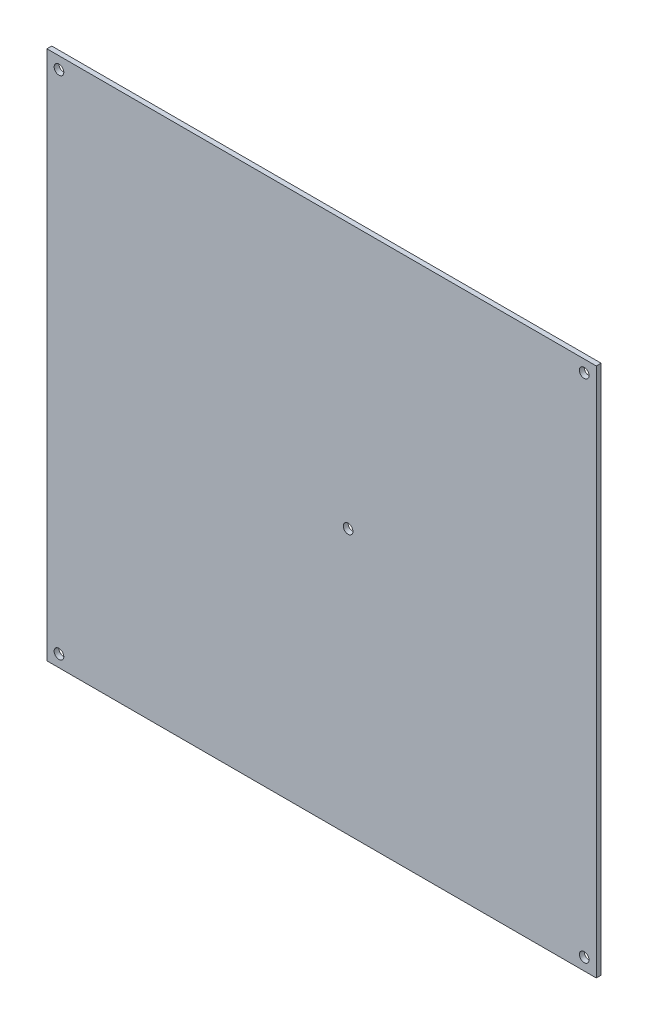
SolidWorks part; units mm, degrees
ref_plane "Alzado" through (0, 0, 0) normal (0, 0, 1) x (1, 0, 0)
ref_plane "Planta" through (0, 0, 0) normal (0, 1, 0) x (1, 0, 0)
ref_plane "Vista lateral" through (0, 0, 0) normal (1, 0, 0) x (0, 0, -1)
sketch "Sketch1" plane through (0, 0, 0) normal (0, 0, 1) x (1, 0, 0)
  line L1 (-83.7545, 63.3993) -> (30.2455, 63.3993)
  line L2 (-83.7545, 63.3993) -> (-83.7545, -46.6007)
  line L3 (-83.7545, -46.6007) -> (30.2455, -46.6007)
  line L4 (30.2455, 63.3993) -> (30.2455, -46.6007)
  line L5 (-83.7545, 63.3993) -> (30.2455, -46.6007) construction
  line L6 (-83.7545, -46.6007) -> (30.2455, 63.3993) construction
  point P0 (-26.7545, 8.3993)
  dimension "D1" = 114
  dimension "D2" = 110
extrude "Boss-Extrude1" add sketch "Sketch1" along normal blind 1
sketch "Sketch2" plane through (0, 0, 1) normal (0, 0, 1) x (1, 0, 0)
  line L0 (-83.7545, 63.3993) -> (-83.7545, -46.6007) construction
  line L9 (30.2455, 63.3993) -> (-83.7545, 63.3993) construction
  line L10 (30.2455, -46.6007) -> (30.2455, 63.3993) construction
  line L11 (-83.7545, -46.6007) -> (30.2455, -46.6007) construction
  circle A1 centre (-81.2545, 60.8993) radius 1
  circle A2 centre (27.7455, 60.8993) radius 1
  circle A3 centre (27.7455, -44.1007) radius 1
  circle A4 centre (-81.2545, -44.1007) radius 1
  dimension "D1" = 2.5
  dimension "D3" = 2.5
  dimension "D5" = 2.5
  dimension "D2" = 2.5
  dimension "D4" = 2.5
  dimension "D6" = 2.5
extrude "Cut-Extrude1" cut sketch "Sketch2" against normal through all
sketch "Sketch3" plane through (0, 0, 0) normal (0, 0, -1) x (-1, 0, 0)
  line L0 (81.2545, 60.8993) -> (81.2545, 11.8993) construction
  line L1 (81.2545, 11.8993) -> (28.7545, 11.8993) construction
  circle A0 centre (28.7545, 11.8993) radius 1
  dimension "D1" = 49
  dimension "D2" = 52.5
extrude "Cut-Extrude2" cut sketch "Sketch3" against normal blind 10
sketch "Sketch4" plane through (0, 0, 1) normal (0, 0, 1) x (1, 0, 0)
  line L1 (-35.1672, 16.8899) -> (-19.4323, 16.8899)
  line L2 (-35.1672, 16.8899) -> (-35.1672, -3.8303)
  line L3 (-35.1672, -3.8303) -> (-19.4323, -3.8303)
  line L4 (-19.4323, 16.8899) -> (-19.4323, -3.8303)
extrude "Boss-Extrude2" add sketch "Sketch4" against normal through all
sketch "Sketch6" plane through (0, 0, 1) normal (0, 0, 1) x (1, 0, 0)
  line L1 (-21.2545, -44.1007) -> (-21.2545, 8.3993) construction
  line L2 (27.7455, -44.1007) -> (-21.2545, -44.1007) construction
  circle A0 centre (-21.2545, 8.3993) radius 1
  dimension "D1" = 52.5
  dimension "D2" = 49
extrude "Cut-Extrude3" cut sketch "Sketch6" against normal blind 10
